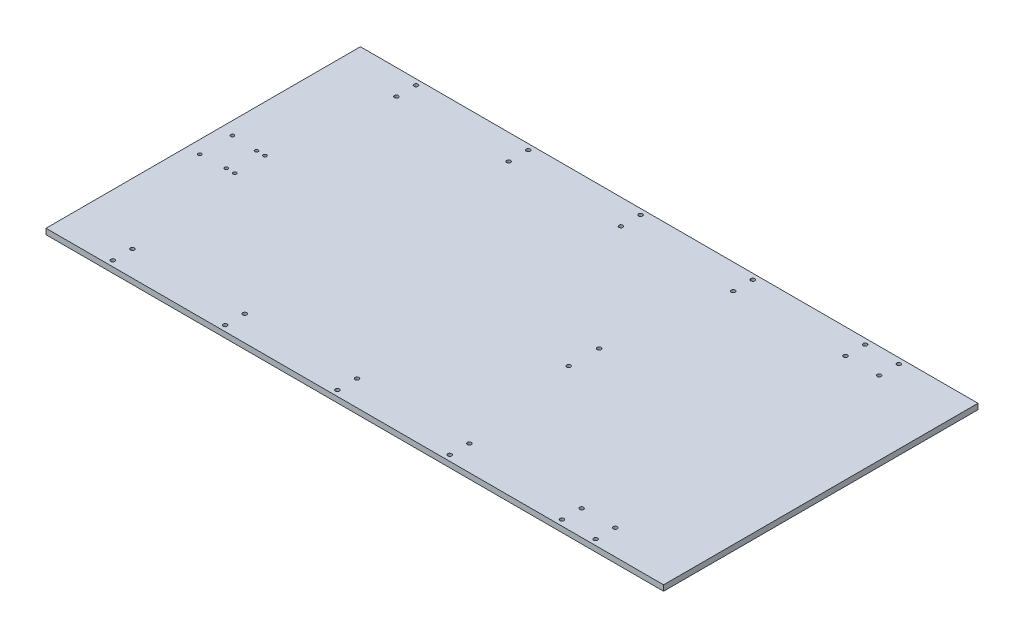
SolidWorks part; units mm, degrees
ref_plane "Спереди" through (0, 0, 0) normal (0, 0, 1) x (1, 0, 0)
ref_plane "Сверху" through (0, 0, 0) normal (0, 1, 0) x (1, 0, 0)
ref_plane "Справа" through (0, 0, 0) normal (1, 0, 0) x (0, 0, -1)
sketch "Эскиз1" plane through (0, 0, 0) normal (0, 1, 0) x (1, 0, 0)
  line L0 (-276.7974, 6.2908) -> (-314.5425, 6.2908) construction
  line L1 (-276.7974, 286.2908) -> (823.2026, 286.2908)
  line L2 (-276.7974, 286.2908) -> (-276.7974, -273.7092)
  line L3 (-276.7974, -273.7092) -> (823.2026, -273.7092)
  line L4 (823.2026, 286.2908) -> (823.2026, -273.7092)
  line L5 (223.2026, 187.065) -> (223.2026, 256.4984) construction
  line L6 (-208.7974, 33.2908) -> (-193.7974, 33.2908) construction
  line L7 (-224.8434, 258.7908) -> (-167.7974, 258.7908) construction
  line L8 (-167.7974, 276.2908) -> (32.2026, 276.2908) construction
  line L9 (632.2026, 276.2908) -> (692.2026, 276.2908) construction
  circle A0 centre (-253.7974, 35.2908) radius 3
  circle A1 centre (-208.7974, 33.2908) radius 3
  circle A2 centre (-193.7974, 33.2908) radius 3
  circle A3 centre (-167.7974, 276.2908) radius 3.5
  circle A4 centre (32.2026, 276.2908) radius 3.5
  circle A5 centre (232.2026, 276.2908) radius 3.5
  circle A6 centre (432.2026, 276.2908) radius 3.5
  circle A7 centre (632.2026, 276.2908) radius 3.5
  circle A8 centre (692.2026, 276.2908) radius 3.5
  circle A9 centre (692.2026, 241.2908) radius 3.5
  circle A10 centre (632.2026, 241.2908) radius 3.5
  circle A11 centre (432.2026, 241.2908) radius 3.5
  circle A12 centre (232.2026, 241.2908) radius 3.5
  circle A13 centre (32.2026, 241.2908) radius 3.5
  circle A14 centre (-167.7974, 241.2908) radius 3.5
  circle A15 centre (632.2026, -228.7092) radius 3.5
  circle A16 centre (692.2026, -228.7092) radius 3.5
  circle A17 centre (692.2026, -263.7092) radius 3.5
  circle A18 centre (632.2026, -263.7092) radius 3.5
  circle A19 centre (432.2026, -228.7092) radius 3.5
  circle A20 centre (432.2026, -263.7092) radius 3.5
  circle A21 centre (232.2026, -228.7092) radius 3.5
  circle A22 centre (232.2026, -263.7092) radius 3.5
  circle A23 centre (32.2026, -228.7092) radius 3.5
  circle A24 centre (32.2026, -263.7092) radius 3.5
  circle A25 centre (-167.7974, -228.7092) radius 3.5
  circle A26 centre (-167.7974, -263.7092) radius 3.5
  circle A27 centre (401.2026, 33.2908) radius 3.5
  circle A28 centre (401.2026, -20.7092) radius 3.5
  circle A29 centre (-193.7974, -20.7092) radius 3
  circle A30 centre (-208.7974, -20.7092) radius 3
  circle A31 centre (-253.7974, -22.7092) radius 3
  point P12 (0, 0)
  point P80 (0, 0)
  point P82 (0, 0)
  dimension "D3" = 6
  dimension "D10" = 7
  dimension "D18" = 7
  dimension "D1" = 280
  dimension "D2" = 280
  dimension "D4" = 23
  dimension "D5" = 29
  dimension "D9" = 15
  dimension "D11" = 10
  dimension "D12" = 109
  dimension "D13" = 17.5
  dimension "D15" = 200
  dimension "D16" = 60
  dimension "D19" = 27
  dimension "D32" = 678
  dimension "D6" = 1100
  dimension "D8" = 2
  dimension "D14" = 5
  dimension "D17" = 2
extrude "Бобышка-Вытянуть1" add sketch "Эскиз1" along normal blind 10
